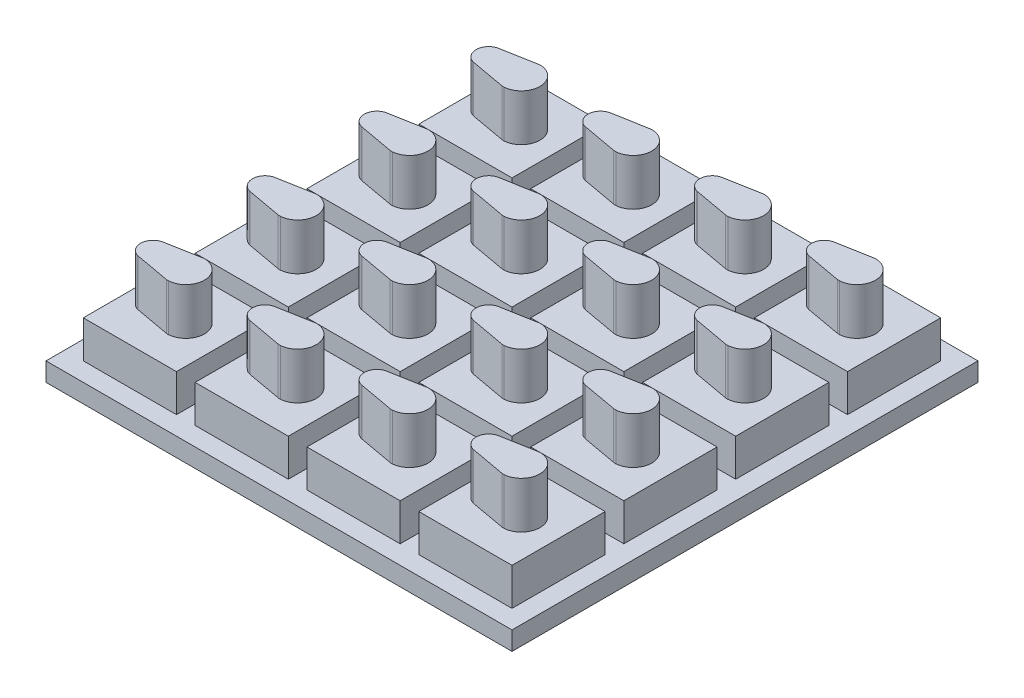
SolidWorks part; units mm, degrees
ref_plane "Front Plane" through (0, 0, 0) normal (0, 0, 1) x (1, 0, 0)
ref_plane "Top Plane" through (0, 0, 0) normal (0, 1, 0) x (1, 0, 0)
ref_plane "Right Plane" through (0, 0, 0) normal (1, 0, 0) x (0, 0, -1)
sketch "Sketch1" plane through (0, 0, 0) normal (0, 1, 0) x (1, 0, 0)
  line L0 (0, 0) -> (-49.3047, 0) construction
  line L1 (-42, 31) -> (-42, 33)
  line L2 (-42, 33) -> (-46, 33)
  line L3 (-46, 33) -> (-46, 29)
  line L4 (-46, 29) -> (-44, 29)
  line L5 (-44, 29) -> (-44, 31)
  line L6 (4, 33) -> (4, 31)
  line L7 (4, 31) -> (6, 31)
  line L8 (6, 29) -> (8, 29)
  line L9 (-8, 5) -> (-18, 5) construction
  line L10 (-8, 7) -> (-15.8633, 7) construction
  line L11 (-8, 17) -> (-14.8417, 17) construction
  line L12 (-8, -5) -> (-16.8168, -5) construction
  line L13 (-8, 29) -> (-13.8882, 29) construction
  line L14 (-8, 19) -> (-12, 19) construction
  line L15 (-8, -7) -> (-15.1823, -7) construction
  line L16 (-8, -17) -> (-14.6374, -17) construction
  line L17 (8, 29) -> (8, 33)
  line L18 (-42, 29) -> (-32, 29)
  line L19 (-42, 29) -> (-42, 19)
  line L20 (-42, 19) -> (-32, 19)
  line L21 (-32, 29) -> (-32, 19)
  line L22 (-30, 29) -> (-20, 29)
  line L23 (-30, 29) -> (-30, 19)
  line L24 (-30, 19) -> (-20, 19)
  line L25 (-20, 29) -> (-20, 19)
  line L26 (-18, 29) -> (-8, 29)
  line L27 (-18, 29) -> (-18, 19)
  line L28 (-18, 19) -> (-8, 19)
  line L29 (-8, 29) -> (-8, 19)
  line L30 (-6, 29) -> (4, 29)
  line L31 (-6, 29) -> (-6, 19)
  line L32 (-6, 19) -> (4, 19)
  line L33 (4, 29) -> (4, 19)
  line L34 (-32, 17) -> (-42, 17)
  line L35 (-32, 17) -> (-32, 7)
  line L36 (-32, 7) -> (-42, 7)
  line L37 (-42, 17) -> (-42, 7)
  line L38 (-30, 17) -> (-20, 17)
  line L39 (-30, 17) -> (-30, 7)
  line L40 (-30, 7) -> (-20, 7)
  line L41 (-20, 17) -> (-20, 7)
  line L42 (-18, 7) -> (-8, 7)
  line L43 (-18, 7) -> (-18, 17)
  line L44 (-18, 17) -> (-8, 17)
  line L45 (-8, 7) -> (-8, 17)
  line L46 (-6, 17) -> (4, 17)
  line L47 (-6, 17) -> (-6, 7)
  line L48 (-6, 7) -> (4, 7)
  line L49 (4, 17) -> (4, 7)
  line L50 (-6, 5) -> (4, 5)
  line L51 (-6, 5) -> (-6, -5)
  line L52 (-6, -5) -> (4, -5)
  line L53 (4, 5) -> (4, -5)
  line L54 (-18, -5) -> (-8, -5)
  line L55 (-18, -5) -> (-18, 5)
  line L56 (-18, 5) -> (-8, 5)
  line L57 (-8, -5) -> (-8, 5)
  line L58 (-20, 5) -> (-30, 5)
  line L59 (-20, 5) -> (-20, -5)
  line L60 (-20, -5) -> (-30, -5)
  line L61 (-30, 5) -> (-30, -5)
  line L62 (-32, -5) -> (-42, -5)
  line L63 (-32, -5) -> (-32, 5)
  line L64 (-32, 5) -> (-42, 5)
  line L65 (-42, -5) -> (-42, 5)
  line L66 (-42, -7) -> (-32, -7)
  line L67 (-42, -7) -> (-42, -17)
  line L68 (-42, -17) -> (-32, -17)
  line L69 (-32, -7) -> (-32, -17)
  line L70 (-30, -7) -> (-20, -7)
  line L71 (-30, -7) -> (-30, -17)
  line L72 (-30, -17) -> (-20, -17)
  line L73 (-20, -7) -> (-20, -17)
  line L74 (-18, -7) -> (-8, -7)
  line L75 (-18, -7) -> (-18, -17)
  line L76 (-18, -17) -> (-8, -17)
  line L77 (-8, -7) -> (-8, -17)
  line L78 (-6, -7) -> (4, -7)
  line L79 (-6, -7) -> (-6, -17)
  line L80 (-6, -17) -> (4, -17)
  line L81 (4, -7) -> (4, -17)
  line L82 (-44, 31) -> (6, 31)
  line L83 (-44, 31) -> (-44, -19)
  line L84 (-44, -19) -> (6, -19)
  line L85 (6, 31) -> (6, -19)
  line L86 (8, 33) -> (4, 33)
  line L87 (4, -19) -> (4, -21)
  line L88 (4, -21) -> (8, -21)
  line L89 (8, -21) -> (8, -17)
  line L90 (8, -17) -> (6, -17)
  line L91 (6, -17) -> (6, -19)
  line L92 (-42, -21) -> (-46, -21)
  line L93 (-46, -21) -> (-46, -17)
  line L94 (-46, -17) -> (-44, -17)
  line L95 (-44, -17) -> (-44, -19)
  line L96 (-42, -19) -> (-42, -21)
  point P1 (-12, 12)
  point P3 (-12, 0)
  point P8 (-24, 0)
  point P10 (0, 24)
  point P11 (-24, 12)
  point P12 (0, 12)
  point P13 (0, -12)
  point P14 (-12, -12)
  point P16 (-24, -12)
  point P19 (-36, 12)
  point P21 (-36, 24)
  point P22 (-24, 24)
  point P23 (-12, 24)
  point P24 (-36, 0)
  point P25 (-36, -12)
  point P32 (8, 29)
  point P34 (4, 33)
  point P35 (8, 33)
  point P36 (-46, -19)
  point P37 (-46, -21)
  point P38 (-42, -21)
  point P39 (4, -21)
  point P40 (8, -21)
  point P41 (8, -17)
  line B0 (-0.1035, 1.9813) -> (-3.7918, 1.315)
  line B1 (-3.7918, -1.315) -> (-0.1035, -1.9813)
  arc B2 (-3.9397, 1.2764) -> (-3.9397, -1.2764) centre (-3.5, 0) ccw
  arc B3 (0.1486, 1.9945) -> (0.1486, -1.9945) centre (0, 0) cw
  arc B4 (-3.9397, 1.2764) -> (-3.7918, 1.315) centre (-3.614, 0.3309) cw
  arc B5 (-3.7918, -1.315) -> (-3.9397, -1.2764) centre (-3.614, -0.3309) cw
  arc B6 (0.1486, 1.9945) -> (-0.1035, 1.9813) centre (0.0743, 0.9972) ccw
  arc B7 (0.1486, -1.9945) -> (-0.1035, -1.9813) centre (0.0743, -0.9972) cw
  line B8 (-12.1035, 1.9813) -> (-15.7918, 1.315)
  line B9 (-15.7918, -1.315) -> (-12.1035, -1.9813)
  arc B10 (-15.9397, 1.2764) -> (-15.9397, -1.2764) centre (-15.5, 0) ccw
  arc B11 (-11.8514, 1.9945) -> (-11.8514, -1.9945) centre (-12, 0) cw
  arc B12 (-15.9397, 1.2764) -> (-15.7918, 1.315) centre (-15.614, 0.3309) cw
  arc B13 (-15.7918, -1.315) -> (-15.9397, -1.2764) centre (-15.614, -0.3309) cw
  arc B14 (-11.8514, 1.9945) -> (-12.1035, 1.9813) centre (-11.9257, 0.9972) ccw
  arc B15 (-11.8514, -1.9945) -> (-12.1035, -1.9813) centre (-11.9257, -0.9972) cw
  line B16 (-24.1035, 1.9813) -> (-27.7918, 1.315)
  line B17 (-27.7918, -1.315) -> (-24.1035, -1.9813)
  arc B18 (-27.9397, 1.2764) -> (-27.9397, -1.2764) centre (-27.5, 0) ccw
  arc B19 (-23.8514, 1.9945) -> (-23.8514, -1.9945) centre (-24, 0) cw
  arc B20 (-27.9397, 1.2764) -> (-27.7918, 1.315) centre (-27.614, 0.3309) cw
  arc B21 (-27.7918, -1.315) -> (-27.9397, -1.2764) centre (-27.614, -0.3309) cw
  arc B22 (-23.8514, 1.9945) -> (-24.1035, 1.9813) centre (-23.9257, 0.9972) ccw
  arc B23 (-23.8514, -1.9945) -> (-24.1035, -1.9813) centre (-23.9257, -0.9972) cw
  line B24 (-0.1035, 13.9813) -> (-3.7918, 13.315)
  line B25 (-3.7918, 10.685) -> (-0.1035, 10.0187)
  arc B26 (-3.9397, 13.2764) -> (-3.9397, 10.7236) centre (-3.5, 12) ccw
  arc B27 (0.1486, 13.9945) -> (0.1486, 10.0055) centre (0, 12) cw
  arc B28 (-3.9397, 13.2764) -> (-3.7918, 13.315) centre (-3.614, 12.3309) cw
  arc B29 (-3.7918, 10.685) -> (-3.9397, 10.7236) centre (-3.614, 11.6691) cw
  arc B30 (0.1486, 13.9945) -> (-0.1035, 13.9813) centre (0.0743, 12.9972) ccw
  arc B31 (0.1486, 10.0055) -> (-0.1035, 10.0187) centre (0.0743, 11.0028) cw
  line B32 (-12.1035, 13.9813) -> (-15.7918, 13.315)
  line B33 (-15.7918, 10.685) -> (-12.1035, 10.0187)
  arc B34 (-15.9397, 13.2764) -> (-15.9397, 10.7236) centre (-15.5, 12) ccw
  arc B35 (-11.8514, 13.9945) -> (-11.8514, 10.0055) centre (-12, 12) cw
  arc B36 (-15.9397, 13.2764) -> (-15.7918, 13.315) centre (-15.614, 12.3309) cw
  arc B37 (-15.7918, 10.685) -> (-15.9397, 10.7236) centre (-15.614, 11.6691) cw
  arc B38 (-11.8514, 13.9945) -> (-12.1035, 13.9813) centre (-11.9257, 12.9972) ccw
  arc B39 (-11.8514, 10.0055) -> (-12.1035, 10.0187) centre (-11.9257, 11.0028) cw
  line B40 (-24.1035, 13.9813) -> (-27.7918, 13.315)
  line B41 (-27.7918, 10.685) -> (-24.1035, 10.0187)
  arc B42 (-27.9397, 13.2764) -> (-27.9397, 10.7236) centre (-27.5, 12) ccw
  arc B43 (-23.8514, 13.9945) -> (-23.8514, 10.0055) centre (-24, 12) cw
  arc B44 (-27.9397, 13.2764) -> (-27.7918, 13.315) centre (-27.614, 12.3309) cw
  arc B45 (-27.7918, 10.685) -> (-27.9397, 10.7236) centre (-27.614, 11.6691) cw
  arc B46 (-23.8514, 13.9945) -> (-24.1035, 13.9813) centre (-23.9257, 12.9972) ccw
  arc B47 (-23.8514, 10.0055) -> (-24.1035, 10.0187) centre (-23.9257, 11.0028) cw
  line B48 (-12.1035, -10.0187) -> (-15.7918, -10.685)
  line B49 (-15.7918, -13.315) -> (-12.1035, -13.9813)
  arc B50 (-15.9397, -10.7236) -> (-15.9397, -13.2764) centre (-15.5, -12) ccw
  arc B51 (-11.8514, -10.0055) -> (-11.8514, -13.9945) centre (-12, -12) cw
  arc B52 (-15.9397, -10.7236) -> (-15.7918, -10.685) centre (-15.614, -11.6691) cw
  arc B53 (-15.7918, -13.315) -> (-15.9397, -13.2764) centre (-15.614, -12.3309) cw
  arc B54 (-11.8514, -10.0055) -> (-12.1035, -10.0187) centre (-11.9257, -11.0028) ccw
  arc B55 (-11.8514, -13.9945) -> (-12.1035, -13.9813) centre (-11.9257, -12.9972) cw
  line B56 (-0.1035, -10.0187) -> (-3.7918, -10.685)
  line B57 (-3.7918, -13.315) -> (-0.1035, -13.9813)
  arc B58 (-3.9397, -10.7236) -> (-3.9397, -13.2764) centre (-3.5, -12) ccw
  arc B59 (0.1486, -10.0055) -> (0.1486, -13.9945) centre (0, -12) cw
  arc B60 (-3.9397, -10.7236) -> (-3.7918, -10.685) centre (-3.614, -11.6691) cw
  arc B61 (-3.7918, -13.315) -> (-3.9397, -13.2764) centre (-3.614, -12.3309) cw
  arc B62 (0.1486, -10.0055) -> (-0.1035, -10.0187) centre (0.0743, -11.0028) ccw
  arc B63 (0.1486, -13.9945) -> (-0.1035, -13.9813) centre (0.0743, -12.9972) cw
  line B64 (-24.1035, -10.0187) -> (-27.7918, -10.685)
  line B65 (-27.7918, -13.315) -> (-24.1035, -13.9813)
  arc B66 (-27.9397, -10.7236) -> (-27.9397, -13.2764) centre (-27.5, -12) ccw
  arc B67 (-23.8514, -10.0055) -> (-23.8514, -13.9945) centre (-24, -12) cw
  arc B68 (-27.9397, -10.7236) -> (-27.7918, -10.685) centre (-27.614, -11.6691) cw
  arc B69 (-27.7918, -13.315) -> (-27.9397, -13.2764) centre (-27.614, -12.3309) cw
  arc B70 (-23.8514, -10.0055) -> (-24.1035, -10.0187) centre (-23.9257, -11.0028) ccw
  arc B71 (-23.8514, -13.9945) -> (-24.1035, -13.9813) centre (-23.9257, -12.9972) cw
  line B72 (-0.1035, 25.9813) -> (-3.7918, 25.315)
  line B73 (-3.7918, 22.685) -> (-0.1035, 22.0187)
  arc B74 (-3.9397, 25.2764) -> (-3.9397, 22.7236) centre (-3.5, 24) ccw
  arc B75 (0.1486, 25.9945) -> (0.1486, 22.0055) centre (0, 24) cw
  arc B76 (-3.9397, 25.2764) -> (-3.7918, 25.315) centre (-3.614, 24.3309) cw
  arc B77 (-3.7918, 22.685) -> (-3.9397, 22.7236) centre (-3.614, 23.6691) cw
  arc B78 (0.1486, 25.9945) -> (-0.1035, 25.9813) centre (0.0743, 24.9972) ccw
  arc B79 (0.1486, 22.0055) -> (-0.1035, 22.0187) centre (0.0743, 23.0028) cw
  line B80 (-12.1035, 25.9813) -> (-15.7918, 25.315)
  line B81 (-15.7918, 22.685) -> (-12.1035, 22.0187)
  arc B82 (-15.9397, 25.2764) -> (-15.9397, 22.7236) centre (-15.5, 24) ccw
  arc B83 (-11.8514, 25.9945) -> (-11.8514, 22.0055) centre (-12, 24) cw
  arc B84 (-15.9397, 25.2764) -> (-15.7918, 25.315) centre (-15.614, 24.3309) cw
  arc B85 (-15.7918, 22.685) -> (-15.9397, 22.7236) centre (-15.614, 23.6691) cw
  arc B86 (-11.8514, 25.9945) -> (-12.1035, 25.9813) centre (-11.9257, 24.9972) ccw
  arc B87 (-11.8514, 22.0055) -> (-12.1035, 22.0187) centre (-11.9257, 23.0028) cw
  line B88 (-24.1035, 25.9813) -> (-27.7918, 25.315)
  line B89 (-27.7918, 22.685) -> (-24.1035, 22.0187)
  arc B90 (-27.9397, 25.2764) -> (-27.9397, 22.7236) centre (-27.5, 24) ccw
  arc B91 (-23.8514, 25.9945) -> (-23.8514, 22.0055) centre (-24, 24) cw
  arc B92 (-27.9397, 25.2764) -> (-27.7918, 25.315) centre (-27.614, 24.3309) cw
  arc B93 (-27.7918, 22.685) -> (-27.9397, 22.7236) centre (-27.614, 23.6691) cw
  arc B94 (-23.8514, 25.9945) -> (-24.1035, 25.9813) centre (-23.9257, 24.9972) ccw
  arc B95 (-23.8514, 22.0055) -> (-24.1035, 22.0187) centre (-23.9257, 23.0028) cw
  line B96 (-36.1035, -10.0187) -> (-39.7918, -10.685)
  line B97 (-39.7918, -13.315) -> (-36.1035, -13.9813)
  arc B98 (-39.9397, -10.7236) -> (-39.9397, -13.2764) centre (-39.5, -12) ccw
  arc B99 (-35.8514, -10.0055) -> (-35.8514, -13.9945) centre (-36, -12) cw
  arc B100 (-39.9397, -10.7236) -> (-39.7918, -10.685) centre (-39.614, -11.6691) cw
  arc B101 (-39.7918, -13.315) -> (-39.9397, -13.2764) centre (-39.614, -12.3309) cw
  arc B102 (-35.8514, -10.0055) -> (-36.1035, -10.0187) centre (-35.9257, -11.0028) ccw
  arc B103 (-35.8514, -13.9945) -> (-36.1035, -13.9813) centre (-35.9257, -12.9972) cw
  line B104 (-36.1035, 25.9813) -> (-39.7918, 25.315)
  line B105 (-39.7918, 22.685) -> (-36.1035, 22.0187)
  arc B106 (-39.9397, 25.2764) -> (-39.9397, 22.7236) centre (-39.5, 24) ccw
  arc B107 (-35.8514, 25.9945) -> (-35.8514, 22.0055) centre (-36, 24) cw
  arc B108 (-39.9397, 25.2764) -> (-39.7918, 25.315) centre (-39.614, 24.3309) cw
  arc B109 (-39.7918, 22.685) -> (-39.9397, 22.7236) centre (-39.614, 23.6691) cw
  arc B110 (-35.8514, 25.9945) -> (-36.1035, 25.9813) centre (-35.9257, 24.9972) ccw
  arc B111 (-35.8514, 22.0055) -> (-36.1035, 22.0187) centre (-35.9257, 23.0028) cw
  line B112 (-36.1035, 1.9813) -> (-39.7918, 1.315)
  line B113 (-39.7918, -1.315) -> (-36.1035, -1.9813)
  arc B114 (-39.9397, 1.2764) -> (-39.9397, -1.2764) centre (-39.5, 0) ccw
  arc B115 (-35.8514, 1.9945) -> (-35.8514, -1.9945) centre (-36, 0) cw
  arc B116 (-39.9397, 1.2764) -> (-39.7918, 1.315) centre (-39.614, 0.3309) cw
  arc B117 (-39.7918, -1.315) -> (-39.9397, -1.2764) centre (-39.614, -0.3309) cw
  arc B118 (-35.8514, 1.9945) -> (-36.1035, 1.9813) centre (-35.9257, 0.9972) ccw
  arc B119 (-35.8514, -1.9945) -> (-36.1035, -1.9813) centre (-35.9257, -0.9972) cw
  line B120 (-36.1035, 13.9813) -> (-39.7918, 13.315)
  line B121 (-39.7918, 10.685) -> (-36.1035, 10.0187)
  arc B122 (-39.9397, 13.2764) -> (-39.9397, 10.7236) centre (-39.5, 12) ccw
  arc B123 (-35.8514, 13.9945) -> (-35.8514, 10.0055) centre (-36, 12) cw
  arc B124 (-39.9397, 13.2764) -> (-39.7918, 13.315) centre (-39.614, 12.3309) cw
  arc B125 (-39.7918, 10.685) -> (-39.9397, 10.7236) centre (-39.614, 11.6691) cw
  arc B126 (-35.8514, 13.9945) -> (-36.1035, 13.9813) centre (-35.9257, 12.9972) ccw
  arc B127 (-35.8514, 10.0055) -> (-36.1035, 10.0187) centre (-35.9257, 11.0028) cw
sketch_block_instance "Block1-4"
sketch_block "Block1"
sketch_block_instance "Block1-6"
sketch_block_instance "Block1-7"
sketch_block_instance "Block1-8"
sketch_block_instance "Block1-9"
sketch_block_instance "Block1-10"
sketch_block_instance "Block1-14"
sketch_block_instance "Block1-15"
sketch_block_instance "Block1-16"
sketch_block_instance "Block1-17"
sketch_block_instance "Block1-18"
sketch_block_instance "Block1-19"
sketch_block_instance "Block1-20"
sketch_block_instance "Block1-21"
sketch_block_instance "Block1-22"
sketch_block_instance "Block1-23"
extrude "Boss-Extrude10" add sketch "Sketch1" along normal blind 11
extrude "Boss-Extrude11" add sketch "Sketch1<21>" along normal blind 6 contours L69 L66 L67 L68 B99 B103 B97 B101 B98 B100 B96 B102 | L65 L62 L63 L64 B115 B119 B113 B117 B114 B116 B112 B118 | L34 L37 L36 L35 B123 B127 B121 B125 B122 B124 B120 B126 | L21 L18 L19 L20 B107 B111 B105 B109 B106 B108 B104 B110 | L25 L22 L23 L24 B91 B95 B89 B93 B90 B92 B88 B94 | L41 L38 L39 L40 B43 B47 B41 B45 B42 B44 B40 B46 | L29 L26 L27 L28 B83 B87 B81 B85 B82 B84 B80 B86 | L33 L30 L31 L32 B75 B79 B73 B77 B74 B76 B72 B78 | L42 L45 L44 L43 B35 B39 B33 B37 B34 B36 B32 B38 | L49 L46 L47 L48 B27 B31 B25 B29 B26 B28 B24 B30 | L54 L57 L56 L55 B11 B15 B9 B13 B10 B12 B8 B14 | L58 L61 L60 L59 B19 B23 B17 B21 B18 B20 B16 B22 | L73 L70 L71 L72 B67 B71 B65 B69 B66 B68 B64 B70 | L77 L74 L75 L76 B51 B55 B49 B53 B50 B52 B48 B54 | L81 L78 L79 L80 B59 B63 B57 B61 B58 B60 B56 B62 | L53 L50 L51 L52 B3 B7 B1 B5 B2 B4 B0 B6 region at (-37, 0, -28.8586) region at (-25, 0, -28.8586) region at (-13, 0, -28.8586) region at (-1, 0, -28.8586) region at (-32.1414, 0, -12) region at (-25, 0, -16.8586) region at (-17.8586, 0, -12) region at (-1, 0, -16.8586) region at (-1, 0, -4.8586) region at (-17.8586, 0, 0) region at (-20.1414, 0, 0) region at (-37, 0, 4.8586) region at (-37, 0, 7.1414) region at (-25, 0, 7.1414) region at (-13, 0, 7.1414) region at (-1, 0, 7.1414)
sketch "Sketch1<21>" plane through (0, 0, 0) normal (0, 1, 0) x (1, 0, 0) same geometry as "Sketch1"
extrude "Boss-Extrude12" add sketch "Sketch1<22>" along normal blind 2 contours L85 L7 L82 L5 L83 L84 L74 L77 L76 L75 L66 L69 L68 L67 L50 L53 L52 L51 L38 L41 L40 L39 L37 L34 L35 L36 L26 L29 L28 L27 L18 L21 L20 L19 L22 L25 L24 region at (-19, 0, -6)
sketch "Sketch1<22>" plane through (0, 0, 0) normal (0, 1, 0) x (1, 0, 0) same geometry as "Sketch1"
